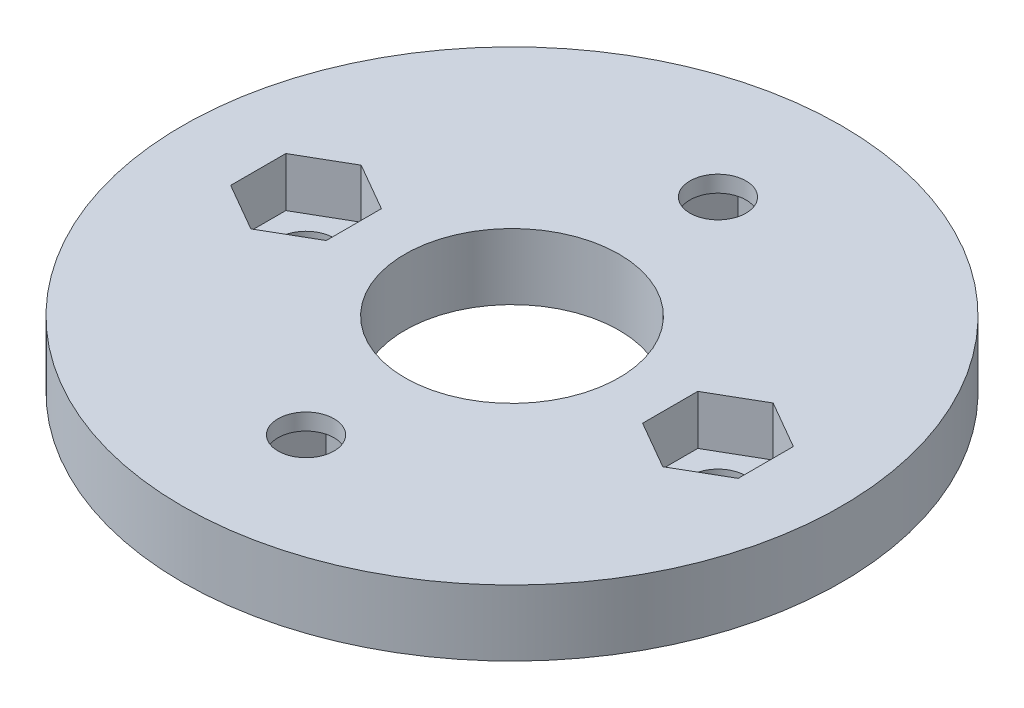
SolidWorks part; units mm, degrees
ref_plane "Спереди" through (0, 0, 0) normal (0, 0, 1) x (1, 0, 0)
ref_plane "Сверху" through (0, 0, 0) normal (0, 1, 0) x (1, 0, 0)
ref_plane "Справа" through (0, 0, 0) normal (1, 0, 0) x (0, 0, -1)
sketch "Эскиз1" plane through (0, 0, 0) normal (0, 1, 0) x (1, 0, 0)
  circle A0 centre (0, 0) radius 20
  circle A1 centre (0, 0) radius 6.5
  dimension "D1" = 13
  dimension "D2" = 40
extrude "тело" add sketch "Эскиз1" along normal blind 4
sketch "Эскиз2" plane through (0, 4, 0) normal (0, 1, 0) x (1, 0, 0)
  line L0 (-15.4, -1.6743) -> (-12.5, -3.3486)
  line L1 (15.4, 1.6743) -> (12.5, 3.3486)
  line L2 (12.5, 3.3486) -> (9.6, 1.6743)
  line L3 (9.6, 1.6743) -> (9.6, -1.6743)
  line L4 (9.6, -1.6743) -> (12.5, -3.3486)
  line L5 (12.5, -3.3486) -> (15.4, -1.6743)
  line L6 (15.4, -1.6743) -> (15.4, 1.6743)
  line L7 (-12.5, -3.3486) -> (-9.6, -1.6743)
  line L8 (-9.6, -1.6743) -> (-9.6, 1.6743)
  line L9 (-9.6, 1.6743) -> (-12.5, 3.3486)
  line L10 (-12.5, 3.3486) -> (-15.4, 1.6743)
  line L11 (-15.4, 1.6743) -> (-15.4, -1.6743)
  circle A0 centre (0, 0) radius 12.5 construction
  circle A1 centre (12.5, 0) radius 2.9 construction
  circle A2 centre (-12.5, 0) radius 2.9 construction
  point P21 (0, 0)
  dimension "D1" = 25
  dimension "D2" = 5.8
  dimension "D3" = 2
extrude "паз для гаек" cut sketch "Эскиз2" against normal blind 3
sketch "Эскиз3" plane through (0, 1, 0) normal (0, 1, 0) x (1, 0, 0)
  line L0 (9.6, 0) -> (15.4, 0) construction
  line L1 (9.6, 1.6743) -> (9.6, -1.6743) construction
  line L2 (15.4, -1.6743) -> (15.4, 1.6743) construction
  circle A0 centre (12.5, 0) radius 1.7
  dimension "D1" = 3.4
extrude "сквозное отверстие под гайкой" cut sketch "Эскиз3" against normal through all and the other way through all
pattern_circular "Круговой массив1" count 4 over 360 about axis through (0, 4, 0) along (0, -1, 0) of "сквозное отверстие под гайкой" reverse direction yes
sketch "Эскиз4" [suppressed] plane through (0, 4, 0) normal (0, 1, 0) x (1, 0, 0)
  circle A0 centre (0, 0) radius 12.5 construction
  circle A1 centre (0, 12.5) radius 1.25
  dimension "D1" = 25
  dimension "D2" = 2.5
extrude "отверстие для шурупа" [suppressed] cut sketch "Эскиз4" against normal through all
sketch "Эскиз5" plane through (0, 0, 0) normal (0, -1, 0) x (1, 0, 0)
  line L1 (3.3486, 12.5) -> (1.6743, 15.4)
  line L2 (1.6743, 15.4) -> (-1.6743, 15.4)
  line L3 (-1.6743, 15.4) -> (-3.3486, 12.5)
  line L4 (-3.3486, 12.5) -> (-1.6743, 9.6)
  line L5 (-1.6743, 9.6) -> (1.6743, 9.6)
  line L6 (1.6743, 9.6) -> (3.3486, 12.5)
  line L12 (-3.3486, -12.5) -> (-1.6743, -15.4)
  line L13 (-1.6743, -15.4) -> (1.6743, -15.4)
  line L14 (1.6743, -15.4) -> (3.3486, -12.5)
  line L15 (3.3486, -12.5) -> (1.6743, -9.6)
  line L16 (1.6743, -9.6) -> (-1.6743, -9.6)
  line L17 (-1.6743, -9.6) -> (-3.3486, -12.5)
  circle A0 centre (0, 12.5) radius 2.9 construction
  circle A1 centre (0, -12.5) radius 2.9 construction
  point P19 (0, 0)
  point P21 (0, 0)
  dimension "D1" = 5.8
  dimension "D2" = 2
extrude "Углубления под гайки с другой стороны" cut sketch "Эскиз5" against normal blind 3
